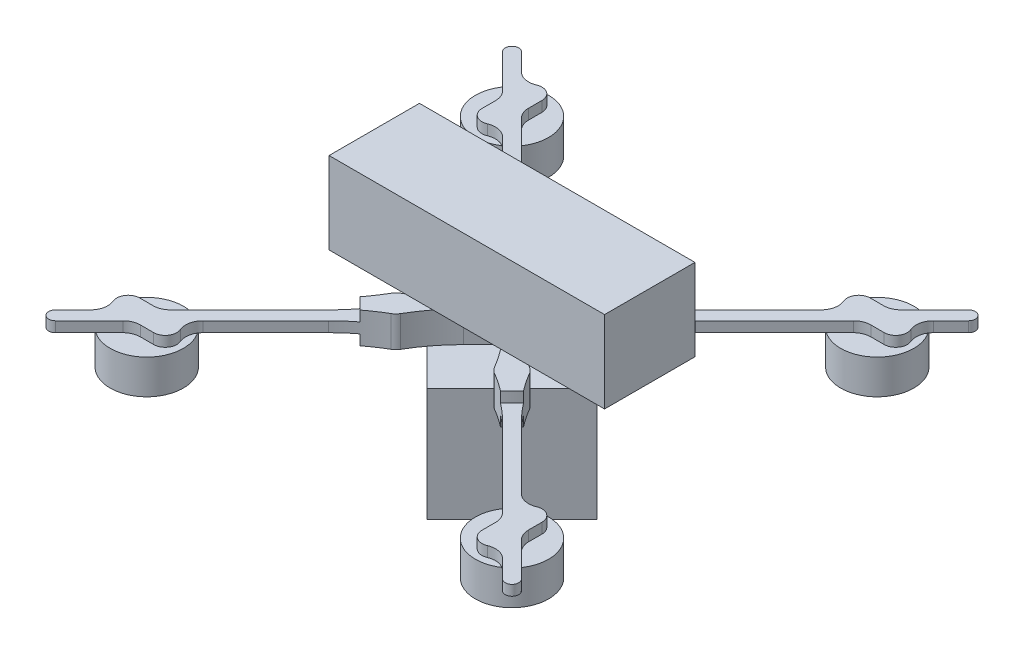
SolidWorks part; units mm, degrees
other "Markup1"
sketch "Sketch7" plane through (54.583, -16.8, -54.583) normal (0.6495, -0.6416, -0.408) x (0.4889, -0.0586, 0.8704)
ref_plane "Front Plane" through (0, 0, 0) normal (0, 0, 1) x (1, 0, 0)
ref_plane "Top Plane" through (0, 0, 0) normal (0, 1, 0) x (1, 0, 0)
ref_plane "Right Plane" through (0, 0, 0) normal (1, 0, 0) x (0, 0, -1)
sketch "Sketch1" plane through (0, 0, 0) normal (0, 1, 0) x (1, 0, 0)
  line L0 (0, 0) -> (0, 62.3643) construction
  line L1 (0, 0) -> (-42.4264, 42.4264) construction
  line L4 (-42.4264, 46.7264) -> (-42.4264, 38.1264) construction
  line L5 (0, 2.192) -> (-51.937, 54.129)
  line L6 (-2.192, 0) -> (-42.9431, 40.751)
  line L7 (-1.096, -1.096) -> (-43.5224, 41.3304) construction
  line L8 (1.096, 1.096) -> (-41.3304, 43.5224) construction
  line L9 (-39.7514, 46.7264) -> (-39.7514, 41.9434)
  line L10 (-45.1014, 38.1264) -> (-45.1014, 42.9094)
  line L11 (-45.1014, 42.9094) -> (-54.129, 51.937)
  line L12 (0, 2.192) -> (0, 0)
  line L13 (0, 0) -> (-2.192, 0)
  arc A2 (-42.4264, 44.0514) -> (-45.051, 47.2431) centre (-42.4264, 46.7264) ccw
  circle A3 centre (-42.4264, 38.1264) radius 2.675
  arc A4 (-51.937, 54.129) -> (-54.129, 51.937) centre (-53.033, 53.033) ccw
  circle A5 centre (-13.4838, 13.4838) radius 3
  point P6 (-42.4264, 42.4264)
  dimension "D7" = 5.35
  dimension "D8" = 6
  dimension "D1" = 60
  dimension "D2" = 45
  dimension "D3" = 8.6
  dimension "D4" = 1.55
  dimension "D5" = 1.55
  dimension "D6" = 75
extrude "Boss-Extrude1" add sketch "Sketch1" along normal blind 2.4 contours L6 A3 | A2 L5 | A2 L5 L9 | L6 A3 | A5 L6 L13 L12 L5 | A5 L5 A4 L11 L10 A3 L6 | A5 region at (-34.7787, 0, -34.7345) region at (-42.1513, 0, -47.0015) region at (-40.4068, 0, -43.8796) region at (-42.7015, 0, -37.8513) region at (-6.0003, 0, -6.0003) region at (-41.0301, 0, -39.5227)
sketch "Sketch6" plane through (0, 0, 0) normal (0, -1, 0) x (1, 0, 0)
  circle A0 centre (-42.4264, -42.4264) radius 8.5
  dimension "D1" = 17
extrude "Boss-Extrude5" add sketch "Sketch6" along normal blind 8 separate body
fillet "Fillet1" radius 4 4 edges at (-39.7514, 1.2, -41.9434) (-45.051, 1.2, -47.2431) (-45.1014, 1.2, -42.9094) (-39.8018, 1.2, -37.6097)
fillet "Fillet2" radius 40 4 edges at (-10.5715, 1.2, -12.7635) (-14.204, 1.2, -16.396) (-16.396, 1.2, -14.204) (-12.7635, 1.2, -10.5715)
pattern_circular "CirPattern3" count 4 over 360 about axis through (0, 2.4, 0) along (0, -1, 0) reverse direction yes of bodies 106
pattern_circular "CirPattern1" count 4 over 360 about axis through (0, 2.4, 0) along (0, -1, 0) of "Boss-Extrude1", "Fillet2", "Fillet1"
sketch "Sketch3" plane through (0, 2.4, 0) normal (0, 1, 0) x (1, 0, 0)
  line L10 (-2.192, 0) -> (-6.7504, -4.5584)
  line L12 (-2.192, 0) -> (-6.7504, -4.5584)
  line L32 (0, 2.192) -> (-4.5584, 6.7504)
  line L33 (-20.2171, 22.4091) -> (-38.5798, 40.7719)
  line L34 (-39.7514, 43.6003) -> (-39.7514, 46.7264)
  line L35 (-47.8541, 50.0461) -> (-51.937, 54.129)
  line L36 (-54.129, 51.937) -> (-46.273, 44.0809)
  line L37 (-45.1014, 41.2525) -> (-45.1014, 38.1264)
  line L38 (-36.9987, 34.8067) -> (-22.4091, 20.2171)
  line L39 (-6.7504, 4.5584) -> (-2.192, 0)
  line L44 (-22.4091, -20.2171) -> (-40.7719, -38.5798)
  line L45 (-22.4091, -20.2171) -> (-40.7719, -38.5798)
  line L46 (-43.6003, -39.7514) -> (-46.7264, -39.7514)
  line L47 (-43.6003, -39.7514) -> (-46.7264, -39.7514)
  line L48 (-50.0461, -47.8541) -> (-54.129, -51.937)
  line L49 (-50.0461, -47.8541) -> (-54.129, -51.937)
  line L50 (-51.937, -54.129) -> (-44.0809, -46.273)
  line L51 (-51.937, -54.129) -> (-44.0809, -46.273)
  line L52 (-41.2525, -45.1014) -> (-38.1264, -45.1014)
  line L53 (-41.2525, -45.1014) -> (-38.1264, -45.1014)
  line L54 (-34.8067, -36.9987) -> (-20.2171, -22.4091)
  line L55 (-34.8067, -36.9987) -> (-20.2171, -22.4091)
  line L56 (-4.5584, -6.7504) -> (0, -2.192)
  line L57 (-4.5584, -6.7504) -> (0, -2.192)
  line L58 (0, -2.192) -> (4.5584, -6.7504)
  line L59 (0, -2.192) -> (4.5584, -6.7504)
  line L60 (20.2171, -22.4091) -> (38.5798, -40.7719)
  line L61 (20.2171, -22.4091) -> (38.5798, -40.7719)
  line L62 (39.7514, -43.6003) -> (39.7514, -46.7264)
  line L63 (39.7514, -43.6003) -> (39.7514, -46.7264)
  line L64 (0, 2.192) -> (-4.5584, 6.7504)
  line L65 (-20.2171, 22.4091) -> (-38.5798, 40.7719)
  line L66 (-39.7514, 43.6003) -> (-39.7514, 46.7264)
  line L67 (-47.8541, 50.0461) -> (-51.937, 54.129)
  line L68 (-54.129, 51.937) -> (-46.273, 44.0809)
  line L69 (-45.1014, 41.2525) -> (-45.1014, 38.1264)
  line L70 (-36.9987, 34.8067) -> (-22.4091, 20.2171)
  line L71 (-6.7504, 4.5584) -> (-2.192, 0)
  line L96 (47.8541, -50.0461) -> (51.937, -54.129)
  line L97 (47.8541, -50.0461) -> (51.937, -54.129)
  line L98 (54.129, -51.937) -> (46.273, -44.0809)
  line L99 (54.129, -51.937) -> (46.273, -44.0809)
  line L100 (45.1014, -41.2525) -> (45.1014, -38.1264)
  line L101 (45.1014, -41.2525) -> (45.1014, -38.1264)
  line L102 (36.9987, -34.8067) -> (22.4091, -20.2171)
  line L103 (36.9987, -34.8067) -> (22.4091, -20.2171)
  line L104 (6.7504, -4.5584) -> (2.192, 0)
  line L105 (6.7504, -4.5584) -> (2.192, 0)
  line L106 (2.192, 0) -> (6.7504, 4.5584)
  line L107 (2.192, 0) -> (6.7504, 4.5584)
  line L108 (22.4091, 20.2171) -> (40.7719, 38.5798)
  line L109 (22.4091, 20.2171) -> (40.7719, 38.5798)
  line L110 (43.6003, 39.7514) -> (46.7264, 39.7514)
  line L111 (43.6003, 39.7514) -> (46.7264, 39.7514)
  line L112 (50.0461, 47.8541) -> (54.129, 51.937)
  line L113 (50.0461, 47.8541) -> (54.129, 51.937)
  line L114 (51.937, 54.129) -> (44.0809, 46.273)
  line L115 (51.937, 54.129) -> (44.0809, 46.273)
  line L116 (41.2525, 45.1014) -> (38.1264, 45.1014)
  line L117 (41.2525, 45.1014) -> (38.1264, 45.1014)
  line L118 (34.8067, 36.9987) -> (20.2171, 22.4091)
  line L119 (34.8067, 36.9987) -> (20.2171, 22.4091)
  line L120 (4.5584, 6.7504) -> (0, 2.192)
  line L121 (4.5584, 6.7504) -> (0, 2.192)
  circle A0 centre (0, 0) radius 25.002
  arc A53 (-10.8878, 14.9873) -> (-4.5584, 6.7504) centre (23.7259, 35.0347) ccw
  arc A54 (-10.8878, 14.9873) -> (-11.9802, 16.0798) centre (-13.4838, 13.4838) ccw
  arc A55 (-20.2171, 22.4091) -> (-11.9802, 16.0798) centre (8.0672, 50.6934) ccw
  arc A56 (-39.7514, 43.6003) -> (-38.5798, 40.7719) centre (-35.7514, 43.6003) ccw
  arc A57 (-39.7514, 46.7264) -> (-43.4681, 49.1903) centre (-42.4264, 46.7264) ccw
  arc A58 (-47.8541, 50.0461) -> (-43.4681, 49.1903) centre (-45.0257, 52.8745) ccw
  arc A59 (-51.937, 54.129) -> (-54.129, 51.937) centre (-53.033, 53.033) ccw
  arc A60 (-45.1014, 41.2525) -> (-46.273, 44.0809) centre (-49.1014, 41.2525) ccw
  arc A61 (-45.1014, 38.1264) -> (-41.3848, 35.6625) centre (-42.4264, 38.1264) ccw
  arc A62 (-36.9987, 34.8067) -> (-41.3848, 35.6625) centre (-39.8272, 31.9783) ccw
  arc A63 (-16.0798, 11.9802) -> (-22.4091, 20.2171) centre (-50.6934, -8.0672) ccw
  arc A64 (-16.0798, 11.9802) -> (-14.9873, 10.8878) centre (-13.4838, 13.4838) ccw
  arc A65 (-6.7504, 4.5584) -> (-14.9873, 10.8878) centre (-35.0347, -23.7259) ccw
  arc A66 (-14.9873, -10.8878) -> (-6.7504, -4.5584) centre (-35.0347, 23.7259) ccw
  arc A67 (-14.9873, -10.8878) -> (-6.7504, -4.5584) centre (-35.0347, 23.7259) ccw
  arc A68 (-14.9873, -10.8878) -> (-16.0798, -11.9802) centre (-13.4838, -13.4838) ccw
  arc A69 (-14.9873, -10.8878) -> (-16.0798, -11.9802) centre (-13.4838, -13.4838) ccw
  arc A70 (-22.4091, -20.2171) -> (-16.0798, -11.9802) centre (-50.6934, 8.0672) ccw
  arc A71 (-22.4091, -20.2171) -> (-16.0798, -11.9802) centre (-50.6934, 8.0672) ccw
  arc A72 (-43.6003, -39.7514) -> (-40.7719, -38.5798) centre (-43.6003, -35.7514) ccw
  arc A73 (-43.6003, -39.7514) -> (-40.7719, -38.5798) centre (-43.6003, -35.7514) ccw
  arc A74 (-46.7264, -39.7514) -> (-49.1903, -43.4681) centre (-46.7264, -42.4264) ccw
  arc A75 (-46.7264, -39.7514) -> (-49.1903, -43.4681) centre (-46.7264, -42.4264) ccw
  arc A76 (-50.0461, -47.8541) -> (-49.1903, -43.4681) centre (-52.8745, -45.0257) ccw
  arc A77 (-50.0461, -47.8541) -> (-49.1903, -43.4681) centre (-52.8745, -45.0257) ccw
  arc A78 (-54.129, -51.937) -> (-51.937, -54.129) centre (-53.033, -53.033) ccw
  arc A79 (-54.129, -51.937) -> (-51.937, -54.129) centre (-53.033, -53.033) ccw
  arc A80 (-41.2525, -45.1014) -> (-44.0809, -46.273) centre (-41.2525, -49.1014) ccw
  arc A81 (-41.2525, -45.1014) -> (-44.0809, -46.273) centre (-41.2525, -49.1014) ccw
  arc A82 (-38.1264, -45.1014) -> (-35.6625, -41.3848) centre (-38.1264, -42.4264) ccw
  arc A83 (-38.1264, -45.1014) -> (-35.6625, -41.3848) centre (-38.1264, -42.4264) ccw
  arc A84 (-34.8067, -36.9987) -> (-35.6625, -41.3848) centre (-31.9783, -39.8272) ccw
  arc A85 (-34.8067, -36.9987) -> (-35.6625, -41.3848) centre (-31.9783, -39.8272) ccw
  arc A86 (-11.9802, -16.0798) -> (-20.2171, -22.4091) centre (8.0672, -50.6934) ccw
  arc A87 (-11.9802, -16.0798) -> (-20.2171, -22.4091) centre (8.0672, -50.6934) ccw
  arc A88 (-11.9802, -16.0798) -> (-10.8878, -14.9873) centre (-13.4838, -13.4838) ccw
  arc A89 (-11.9802, -16.0798) -> (-10.8878, -14.9873) centre (-13.4838, -13.4838) ccw
  arc A90 (-4.5584, -6.7504) -> (-10.8878, -14.9873) centre (23.7259, -35.0347) ccw
  arc A91 (-4.5584, -6.7504) -> (-10.8878, -14.9873) centre (23.7259, -35.0347) ccw
  arc A92 (10.8878, -14.9873) -> (4.5584, -6.7504) centre (-23.7259, -35.0347) ccw
  arc A93 (10.8878, -14.9873) -> (4.5584, -6.7504) centre (-23.7259, -35.0347) ccw
  arc A94 (10.8878, -14.9873) -> (11.9802, -16.0798) centre (13.4838, -13.4838) ccw
  arc A95 (10.8878, -14.9873) -> (11.9802, -16.0798) centre (13.4838, -13.4838) ccw
  arc A96 (20.2171, -22.4091) -> (11.9802, -16.0798) centre (-8.0672, -50.6934) ccw
  arc A97 (20.2171, -22.4091) -> (11.9802, -16.0798) centre (-8.0672, -50.6934) ccw
  arc A98 (39.7514, -43.6003) -> (38.5798, -40.7719) centre (35.7514, -43.6003) ccw
  arc A99 (39.7514, -43.6003) -> (38.5798, -40.7719) centre (35.7514, -43.6003) ccw
  arc A100 (39.7514, -46.7264) -> (43.4681, -49.1903) centre (42.4264, -46.7264) ccw
  arc A101 (39.7514, -46.7264) -> (43.4681, -49.1903) centre (42.4264, -46.7264) ccw
  arc A102 (47.8541, -50.0461) -> (43.4681, -49.1903) centre (45.0257, -52.8745) ccw
  arc A103 (47.8541, -50.0461) -> (43.4681, -49.1903) centre (45.0257, -52.8745) ccw
  arc A104 (51.937, -54.129) -> (54.129, -51.937) centre (53.033, -53.033) ccw
  arc A105 (-10.8878, 14.9873) -> (-4.5584, 6.7504) centre (23.7259, 35.0347) ccw
  arc A106 (-10.8878, 14.9873) -> (-11.9802, 16.0798) centre (-13.4838, 13.4838) ccw
  arc A107 (-20.2171, 22.4091) -> (-11.9802, 16.0798) centre (8.0672, 50.6934) ccw
  arc A108 (-39.7514, 43.6003) -> (-38.5798, 40.7719) centre (-35.7514, 43.6003) ccw
  arc A109 (-39.7514, 46.7264) -> (-43.4681, 49.1903) centre (-42.4264, 46.7264) ccw
  arc A110 (-47.8541, 50.0461) -> (-43.4681, 49.1903) centre (-45.0257, 52.8745) ccw
  arc A111 (-51.937, 54.129) -> (-54.129, 51.937) centre (-53.033, 53.033) ccw
  arc A112 (-45.1014, 41.2525) -> (-46.273, 44.0809) centre (-49.1014, 41.2525) ccw
  arc A113 (-45.1014, 38.1264) -> (-41.3848, 35.6625) centre (-42.4264, 38.1264) ccw
  arc A114 (-36.9987, 34.8067) -> (-41.3848, 35.6625) centre (-39.8272, 31.9783) ccw
  arc A115 (-16.0798, 11.9802) -> (-22.4091, 20.2171) centre (-50.6934, -8.0672) ccw
  arc A116 (-16.0798, 11.9802) -> (-14.9873, 10.8878) centre (-13.4838, 13.4838) ccw
  arc A117 (-6.7504, 4.5584) -> (-14.9873, 10.8878) centre (-35.0347, -23.7259) ccw
  arc A157 (51.937, -54.129) -> (54.129, -51.937) centre (53.033, -53.033) ccw
  arc A158 (45.1014, -41.2525) -> (46.273, -44.0809) centre (49.1014, -41.2525) ccw
  arc A159 (45.1014, -41.2525) -> (46.273, -44.0809) centre (49.1014, -41.2525) ccw
  arc A160 (45.1014, -38.1264) -> (41.3848, -35.6625) centre (42.4264, -38.1264) ccw
  arc A161 (45.1014, -38.1264) -> (41.3848, -35.6625) centre (42.4264, -38.1264) ccw
  arc A162 (36.9987, -34.8067) -> (41.3848, -35.6625) centre (39.8272, -31.9783) ccw
  arc A163 (36.9987, -34.8067) -> (41.3848, -35.6625) centre (39.8272, -31.9783) ccw
  arc A164 (16.0798, -11.9802) -> (22.4091, -20.2171) centre (50.6934, 8.0672) ccw
  arc A165 (16.0798, -11.9802) -> (22.4091, -20.2171) centre (50.6934, 8.0672) ccw
  arc A166 (16.0798, -11.9802) -> (14.9873, -10.8878) centre (13.4838, -13.4838) ccw
  arc A167 (16.0798, -11.9802) -> (14.9873, -10.8878) centre (13.4838, -13.4838) ccw
  arc A168 (6.7504, -4.5584) -> (14.9873, -10.8878) centre (35.0347, 23.7259) ccw
  arc A169 (6.7504, -4.5584) -> (14.9873, -10.8878) centre (35.0347, 23.7259) ccw
  arc A170 (14.9873, 10.8878) -> (6.7504, 4.5584) centre (35.0347, -23.7259) ccw
  arc A171 (14.9873, 10.8878) -> (6.7504, 4.5584) centre (35.0347, -23.7259) ccw
  arc A172 (14.9873, 10.8878) -> (16.0798, 11.9802) centre (13.4838, 13.4838) ccw
  arc A173 (14.9873, 10.8878) -> (16.0798, 11.9802) centre (13.4838, 13.4838) ccw
  arc A174 (22.4091, 20.2171) -> (16.0798, 11.9802) centre (50.6934, -8.0672) ccw
  arc A175 (22.4091, 20.2171) -> (16.0798, 11.9802) centre (50.6934, -8.0672) ccw
  arc A176 (43.6003, 39.7514) -> (40.7719, 38.5798) centre (43.6003, 35.7514) ccw
  arc A177 (43.6003, 39.7514) -> (40.7719, 38.5798) centre (43.6003, 35.7514) ccw
  arc A178 (46.7264, 39.7514) -> (49.1903, 43.4681) centre (46.7264, 42.4264) ccw
  arc A179 (46.7264, 39.7514) -> (49.1903, 43.4681) centre (46.7264, 42.4264) ccw
  arc A180 (50.0461, 47.8541) -> (49.1903, 43.4681) centre (52.8745, 45.0257) ccw
  arc A181 (50.0461, 47.8541) -> (49.1903, 43.4681) centre (52.8745, 45.0257) ccw
  arc A182 (54.129, 51.937) -> (51.937, 54.129) centre (53.033, 53.033) ccw
  arc A183 (54.129, 51.937) -> (51.937, 54.129) centre (53.033, 53.033) ccw
  arc A184 (41.2525, 45.1014) -> (44.0809, 46.273) centre (41.2525, 49.1014) ccw
  arc A185 (41.2525, 45.1014) -> (44.0809, 46.273) centre (41.2525, 49.1014) ccw
  arc A186 (38.1264, 45.1014) -> (35.6625, 41.3848) centre (38.1264, 42.4264) ccw
  arc A187 (38.1264, 45.1014) -> (35.6625, 41.3848) centre (38.1264, 42.4264) ccw
  arc A188 (34.8067, 36.9987) -> (35.6625, 41.3848) centre (31.9783, 39.8272) ccw
  arc A189 (34.8067, 36.9987) -> (35.6625, 41.3848) centre (31.9783, 39.8272) ccw
  arc A190 (11.9802, 16.0798) -> (20.2171, 22.4091) centre (-8.0672, 50.6934) ccw
  arc A191 (11.9802, 16.0798) -> (20.2171, 22.4091) centre (-8.0672, 50.6934) ccw
  arc A192 (11.9802, 16.0798) -> (10.8878, 14.9873) centre (13.4838, 13.4838) ccw
  arc A193 (11.9802, 16.0798) -> (10.8878, 14.9873) centre (13.4838, 13.4838) ccw
  arc A194 (4.5584, 6.7504) -> (10.8878, 14.9873) centre (-23.7259, 35.0347) ccw
  arc A195 (4.5584, 6.7504) -> (10.8878, 14.9873) centre (-23.7259, 35.0347) ccw
  dimension "D1" = 0
extrude "Boss-Extrude2" add sketch "Sketch3" along normal blind 2.4 and the other way blind 4.8 contours A195 L121 L64 A105 A106 A107 A0 A115 A116 A117 L71 L12 A67 A69 A71 A87 A89 A91 L57 L59 A93 A95 A97 A165 A167 A169 L105 L107 A171 A173 A175 A191 A193 region at (0, 2.4, 0)
sketch "Sketch4" plane through (0, -2.4, 0) normal (0, -1, 0) x (1, 0, 0)
  line L1 (-19.799, 0) -> (0, -19.799)
  line L2 (-19.799, 0) -> (0, 19.799)
  line L3 (0, 19.799) -> (19.799, 0)
  line L4 (0, -19.799) -> (19.799, 0)
  line L5 (-19.799, 0) -> (19.799, 0) construction
  line L6 (0, 19.799) -> (0, -19.799) construction
  point P0 (0, 0)
  dimension "D1" = 28
extrude "Boss-Extrude3" add sketch "Sketch4" along normal blind 26.4 separate body
sketch "Sketch5" plane through (0, 4.8, 0) normal (0, 1, 0) x (1, 0, 0)
  line L1 (-32, -10.5) -> (32, -10.5)
  line L2 (-32, -10.5) -> (-32, 10.5)
  line L3 (-32, 10.5) -> (32, 10.5)
  line L4 (32, -10.5) -> (32, 10.5)
  line L5 (-32, -10.5) -> (32, 10.5) construction
  line L6 (-32, 10.5) -> (32, -10.5) construction
  point P0 (0, 0)
  dimension "D1" = 21
  dimension "D2" = 64
extrude "Boss-Extrude4" add sketch "Sketch5" along normal blind 19 separate body
